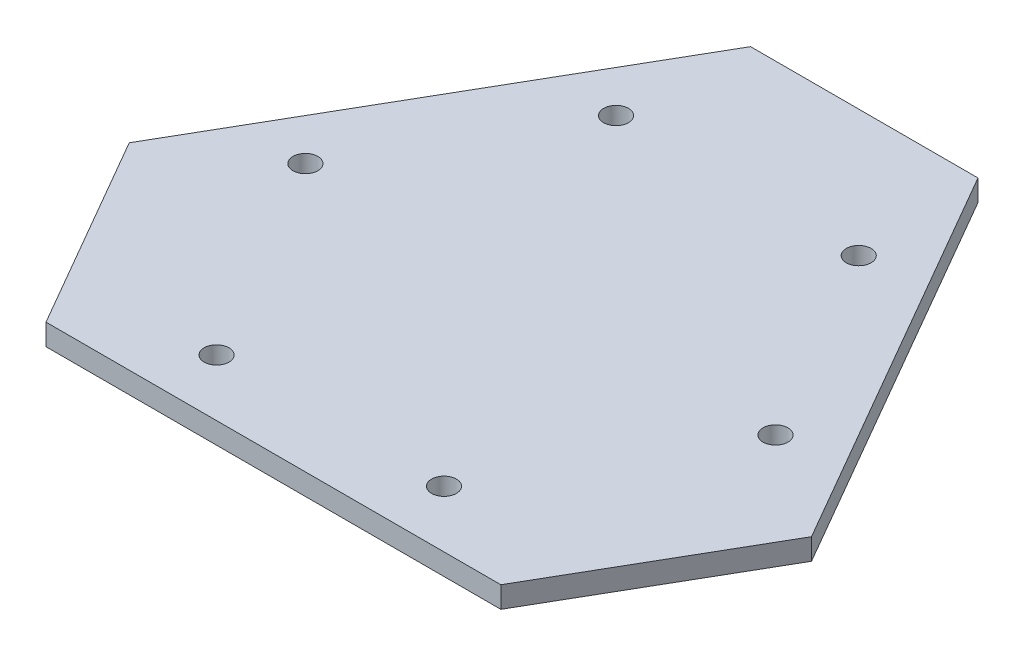
SolidWorks part; units mm, degrees
ref_plane "Front Plane" through (0, 0, 0) normal (0, 0, 1) x (1, 0, 0)
ref_plane "Top Plane" through (0, 0, 0) normal (0, 1, 0) x (1, 0, 0)
ref_plane "Right Plane" through (0, 0, 0) normal (1, 0, 0) x (0, 0, -1)
sketch "Sketch1" plane through (0, 0, 0) normal (0, 1, 0) x (1, 0, 0)
  line L0 (-50.8, 146.647) -> (50.8, 146.647)
  line L1 (50.8, 146.647) -> (152.4, -29.3294)
  line L2 (152.4, -29.3294) -> (101.6, -117.3176)
  line L3 (101.6, -117.3176) -> (-101.6, -117.3176)
  line L4 (-101.6, -117.3176) -> (-152.4, -29.3294)
  line L5 (-152.4, -29.3294) -> (-50.8, 146.647)
  line L6 (0, 0) -> (-101.6, 58.6588) construction
  line L7 (0, 146.647) -> (0, 0) construction
  line L8 (0, 0) -> (-127, -73.3235) construction
  line L9 (0, 0) -> (127, -73.3235) construction
  line L10 (0, 0) -> (101.6, 58.6588) construction
  line L11 (50.8, 146.647) -> (6.8059, 121.247) construction
  line L12 (6.8059, 121.247) -> (123.0706, -80.1294) construction
  line L13 (0, 0) -> (0, -117.3176) construction
  dimension "D1" = 101.6
  dimension "D2" = 203.2
  dimension "D3" = 50.8
extrude "Boss-Extrude1" add sketch "Sketch1" along normal mid plane 9.525
sketch "Sketch2" plane through (0, 4.7625, 0) normal (0, 1, 0) x (1, 0, 0)
  line L0 (101.6, 58.6588) -> (57.6059, 33.2588) construction
  line L1 (152.4, -29.3294) -> (50.8, 146.647) construction
  line L2 (54.203, 89.9529) -> (105.003, 1.9647) construction
  circle A0 centre (105.003, 1.9647) radius 5.5563
  circle A1 centre (54.203, 89.9529) radius 5.5562
  point P6 (79.603, 45.9588)
  dimension "D3" = 11.1125
  dimension "D1" = 50.8
  dimension "D2" = 101.6
extrude "Cut-Extrude1" cut sketch "Sketch2" against normal through all
ref_axis "Axis1" through (0, 5.2388, 0) along (0, -1, 0)
pattern_circular "CirPattern1" count 3 over 360 about axis through (0, 5.2388, 0) along (0, -1, 0) of "Cut-Extrude1"
